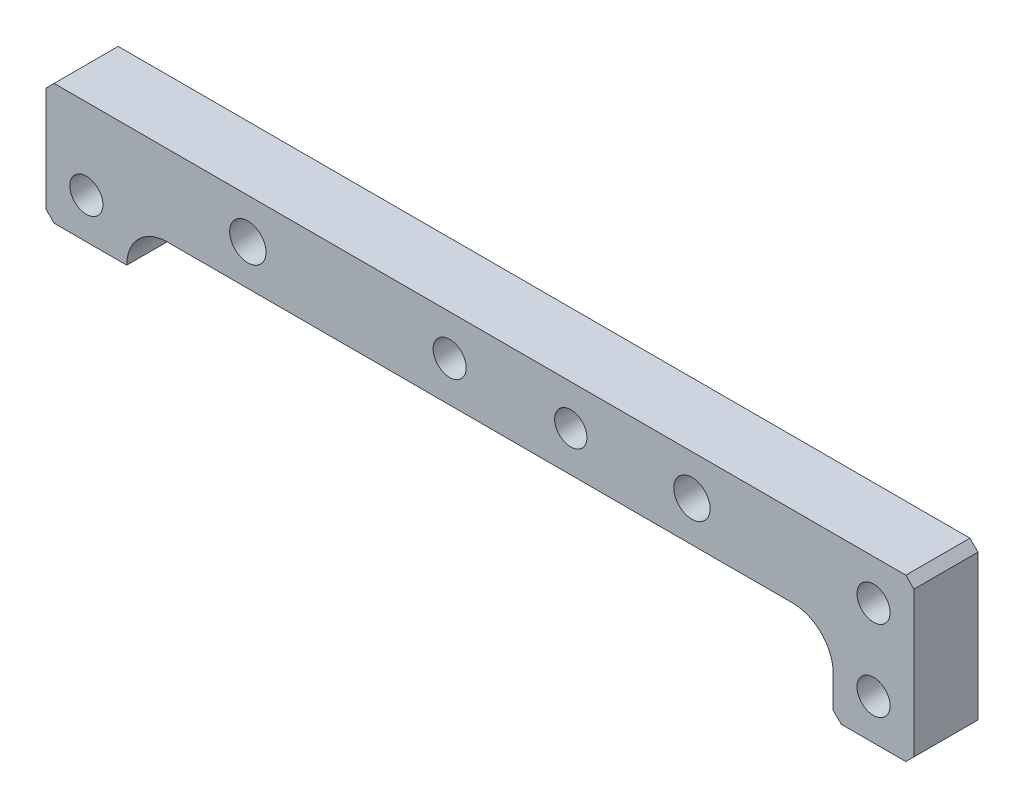
SolidWorks part; units mm, degrees
ref_plane "前视基准面" through (0, 0, 0) normal (0, 0, 1) x (1, 0, 0)
ref_plane "上视基准面" through (0, 0, 0) normal (0, 1, 0) x (1, 0, 0)
ref_plane "右视基准面" through (0, 0, 0) normal (1, 0, 0) x (0, 0, -1)
sketch "草图1" plane through (0, 0, 0) normal (0, 0, 1) x (1, 0, 0)
  line L0 (0, 0) -> (-30, 0) construction
  line L1 (0, 0) -> (0, 10) construction
  line L3 (45, 10) -> (-45, 10) construction
  line L8 (0, 10) -> (-130, 10)
  line L9 (-130, 10) -> (-130, -20)
  line L15 (0, -10) -> (-110, -10)
  line L20 (0, 0) -> (0, -10) construction
  line L21 (-110, -10) -> (-110, -20)
  line L22 (75, 0) -> (75, -20) construction
  line L24 (85, 10) -> (85, -30)
  line L25 (85, -30) -> (65, -30)
  line L26 (65, -30) -> (65, -10)
  line L29 (-110, -20) -> (-130, -20)
  line L30 (-110, -10) -> (-120, -10) construction
  line L31 (0, 10) -> (85, 10)
  line L32 (65, -10) -> (0, -10)
  circle A0 centre (0, 0) radius 4
  circle A1 centre (-30, 0) radius 4.1
  circle A4 centre (75, 0) radius 4.1
  circle A5 centre (75, -20) radius 4.1
  circle A6 centre (-120, -10) radius 4.1
  dimension "D1" = 130
  dimension "D5" = 40
  dimension "D2" = 30
  dimension "D3" = 10
  dimension "D4" = 10
  dimension "D6" = 85
  dimension "D7" = 20
extrude "凸台-拉伸1" add sketch "草图1" along normal blind 15.875
fillet "圆角1" radius 10 2 edges at (65, -10, 7.9375) (-110, -10, 7.9375)
chamfer "倒角1" distance 2 angle 45 5 edges at (-130, 10, 7.9375) (-130, -20, 7.9375) (65, -30, 7.9375) (85, -30, 7.9375) (85, 10, 7.9375)
sketch "草图2" plane through (0, 0, 0) normal (0, 0, -1) x (-1, 0, 0)
  line L0 (0, 0) -> (-30, 0) construction
  circle A0 centre (-30, 0) radius 4.5
extrude "切除-拉伸1" cut sketch "草图2" against normal blind 20
sketch "草图3" plane through (0, 0, 0) normal (0, 0, -1) x (-1, 0, 0)
  line L0 (30, 0) -> (80, 0) construction
  circle A0 centre (80, 0) radius 4.5
extrude "切除-拉伸2" cut sketch "草图3" against normal blind 20
